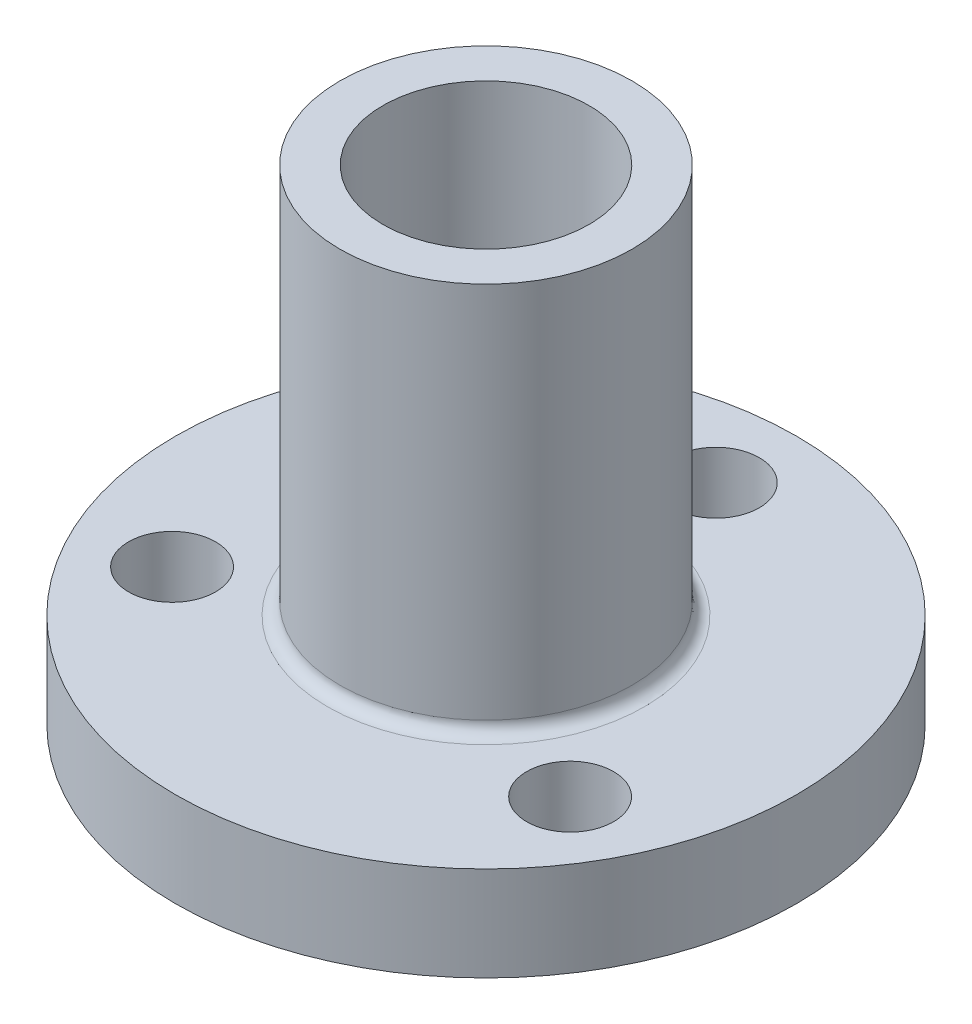
SolidWorks part; units mm, degrees
ref_plane "Plano frontal" through (0, 0, 0) normal (0, 0, 1) x (1, 0, 0)
ref_plane "Plano superior" through (0, 0, 0) normal (0, 1, 0) x (1, 0, 0)
ref_plane "Plano direito" through (0, 0, 0) normal (1, 0, 0) x (0, 0, -1)
sketch "Esboço1" plane through (0, 0, 0) normal (0, 1, 0) x (1, 0, 0)
  line L0 (0, 0) -> (0, -4.15) construction
  circle A0 centre (0, 0) radius 12.5
  circle A1 centre (0, 0) radius 5.875
  circle A2 centre (0, 0) radius 4.15
  circle A3 centre (0, 9.25) radius 1.75
  circle A4 centre (-8.0107, -4.625) radius 1.75
  circle A5 centre (8.0107, -4.625) radius 1.75
  dimension "D1" = 25
  dimension "D2" = 11.75
  dimension "D3" = 8.3
  dimension "D4" = 3.5
  dimension "D5" = 1.5
  dimension "D6" = 1.5
  dimension "D7" = 120
extrude "Ressalto-extrusão1" add sketch "Esboço1" along normal blind 3.8 contours A0 A1 A3 A4 A5 region at (-12.1464, 0, 0)
extrude "Ressalto-extrusão2" add sketch "Esboço1<3>" along normal blind 19.5 contours A1 A2 region at (-5.7088, 0, 0)
sketch "Esboço1<3>" plane through (0, 0, 0) normal (0, 1, 0) x (1, 0, 0) same geometry as "Esboço1"
fillet "Filete1" radius 0.5 1 edges at (0, 3.8, 5.875)
